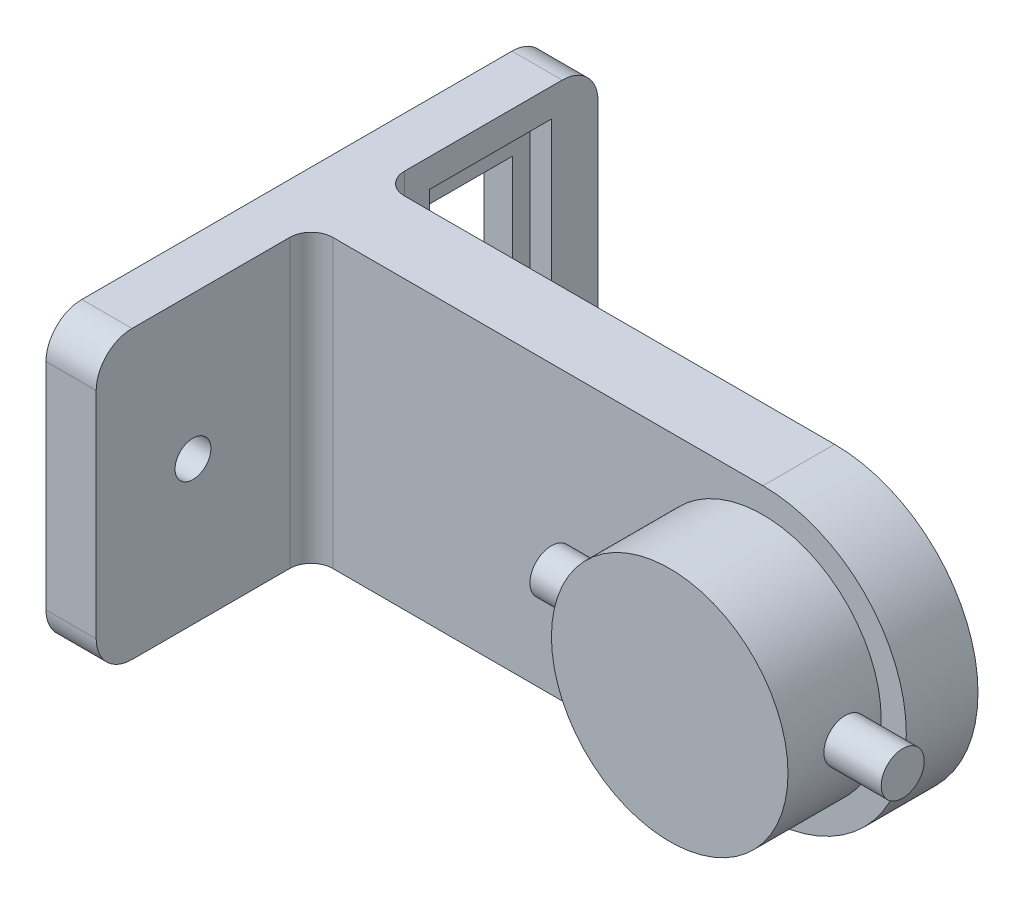
SolidWorks part; units mm, degrees
ref_plane "Front Plane" through (0, 0, 0) normal (0, 0, 1) x (1, 0, 0)
ref_plane "Top Plane" through (0, 0, 0) normal (0, 1, 0) x (1, 0, 0)
ref_plane "Right Plane" through (0, 0, 0) normal (1, 0, 0) x (0, 0, -1)
sketch "Sketch1" plane through (0, 0, 0) normal (0, 0, 1) x (1, 0, 0)
  line L0 (45, 0) -> (25, 0) construction
  line L1 (-45, 20) -> (25, 20)
  line L2 (-45, 20) -> (-45, -20)
  line L3 (-45, -20) -> (25, -20)
  line L5 (-45, 20) -> (45, -20) construction
  line L6 (-45, -20) -> (45, 20) construction
  arc A1 (25, -20) -> (25, 20) centre (25, 0) ccw
  point P0 (0, 0)
  dimension "D1" = 90
  dimension "D2" = 40
extrude "Boss-Extrude1" add sketch "Sketch1" along normal blind 10
sketch "Sketch2" plane through (0, 0, 0) normal (0, 0, -1) x (-1, 0, 0)
  line L0 (45, 20) -> (45, -20)
  line L1 (45, 20) -> (38, 20)
  line L2 (45, -20) -> (38, -20)
  line L3 (38, 20) -> (38, -20)
  dimension "D1" = 7
extrude "Boss-Extrude2" add sketch "Sketch2" along normal blind 30 and the other way blind 40
sketch "Sketch3" plane through (0, 0, 10) normal (0, 0, 1) x (1, 0, 0)
  circle A1 centre (25, 0) radius 16.5
  dimension "D1" = 33
extrude "Boss-Extrude3" add sketch "Sketch3" along normal blind 13 contours A1
sketch "Sketch4" plane through (-38, 0, 0) normal (1, 0, 0) x (0, 0, -1)
  line L3 (6.5, 16.05) -> (23.5, 16.05)
  line L4 (21.075, 11.275) -> (8.925, 11.275)
  line L5 (21.075, 11.275) -> (21.075, -11.275)
  line L6 (21.075, -11.275) -> (8.925, -11.275)
  line L7 (8.925, 11.275) -> (8.925, -11.275)
  line L8 (21.075, 11.275) -> (8.925, -11.275) construction
  line L9 (21.075, -11.275) -> (8.925, 11.275) construction
  line L10 (6.5, 16.05) -> (6.5, -16.05)
  line L11 (6.5, -16.05) -> (23.5, -16.05)
  line L12 (23.5, 16.05) -> (23.5, -16.05)
  line L13 (6.5, 16.05) -> (23.5, -16.05) construction
  line L14 (6.5, -16.05) -> (23.5, 16.05) construction
  point P0 (15, 0)
  point P6 (15, 0)
  dimension "D1" = 22.55
  dimension "D2" = 12.15
  dimension "D3" = 17
  dimension "D4" = 32.1
extrude "Cut-Extrude1" cut sketch "Sketch4" against normal blind 10 contours L4 L7 L6 L5
extrude "Cut-Extrude2" cut sketch "Sketch4<3>" against normal blind 3 contours L3 L12 L11 L10
sketch "Sketch4<3>" plane through (-38, 0, 0) normal (1, 0, 0) x (0, 0, -1) same geometry as "Sketch4"
fillet "Fillet1" radius 3 2 edges at (-38, 0, 10) (-38, 0, 0)
fillet "Fillet2" radius 5 4 edges at (-41.5, -20, 40) (-41.5, 20, 40) (-41.5, -20, -30) (-41.5, 20, -30)
ref_plane "Plane1" through (41.5, 0, 0) normal (1, 0, 0) x (0, 0, -1)
sketch "Sketch5" plane through (41.5, 0, 0) normal (1, 0, 0) x (0, 0, -1)
  circle A0 centre (-15, 0) radius 3
  dimension "D2" = 6
extrude "Boss-Extrude4" add sketch "Sketch5" along normal blind 8 separate body contours A0
pattern_circular "CirPattern3" count 2 over 180 about axis through (25, 0, 23) along (0, 0, -1) of bodies 106
sketch "Sketch6" plane through (-38, 0, 0) normal (1, 0, 0) x (0, 0, -1)
  line L0 (-40, 0) -> (-13, 0) construction
  line L1 (-40, 15) -> (-40, -15) construction
  line L2 (-13, -20) -> (-13, 20) construction
  circle A0 centre (-26.5, 0) radius 2.5
  dimension "D1" = 5
extrude "Cut-Extrude3" cut sketch "Sketch6" against normal blind 7
